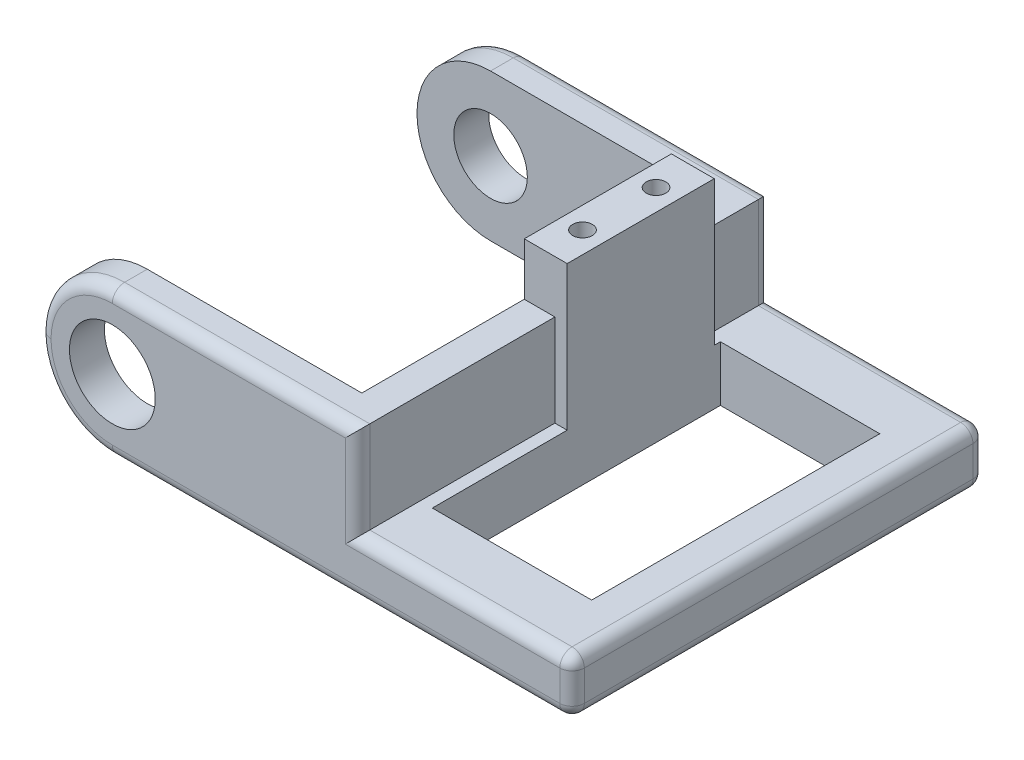
SolidWorks part; units mm, degrees
ref_plane "Front Plane" through (0, 0, 0) normal (0, 0, 1) x (1, 0, 0)
ref_plane "Top Plane" through (0, 0, 0) normal (0, 1, 0) x (1, 0, 0)
ref_plane "Right Plane" through (0, 0, 0) normal (1, 0, 0) x (0, 0, -1)
sketch "Sketch1" plane through (0, 0, 0) normal (1, 0, 0) x (0, 0, -1)
  line L0 (-222.6467, 45.44) -> (-222.6467, 62.0152) construction
  line L1 (-256.3467, 26.069) -> (-222.6467, 26.069)
  line L2 (-256.3467, 26.069) -> (-256.3467, 14.069)
  line L3 (-256.3467, 14.069) -> (-222.6467, 14.069)
  line L4 (-222.6467, 26.069) -> (-222.6467, 14.069)
  dimension "D1" = 12
  dimension "D2" = 33.7
  dimension "D3" = 0
extrude "Boss-Extrude1" add sketch "Sketch1" along normal blind 2.5
sketch "Sketch2" plane through (2.5, 0, 0) normal (1, 0, 0) x (0, 0, -1)
  line L0 (-222.6467, 14.069) -> (-222.6467, 26.069) construction
  line L1 (-256.3467, 14.069) -> (-222.6467, 14.069)
  line L2 (-256.3467, 14.069) -> (-256.3467, 18.569)
  line L3 (-256.3467, 18.569) -> (-222.6467, 18.569)
  line L4 (-222.6467, 14.069) -> (-222.6467, 18.569)
  dimension "D1" = 4.5
extrude "Boss-Extrude2" add sketch "Sketch2" along normal blind 17.5
sketch "Sketch3" plane through (0, 18.569, 0) normal (0, 1, 0) x (1, 0, 0)
  line L0 (2.5, -222.6467) -> (2.5, -256.3467) construction
  line L1 (3.5, -227.7467) -> (16.5, -227.7467)
  line L2 (3.5, -227.7467) -> (3.5, -251.2467)
  line L3 (3.5, -251.2467) -> (16.5, -251.2467)
  line L4 (16.5, -227.7467) -> (16.5, -251.2467)
  line L8 (20, -222.6467) -> (2.5, -222.6467) construction
  dimension "D1" = 1
  dimension "D2" = 23.5
  dimension "D3" = 5.1
  dimension "D4" = 13
extrude "Cut-Extrude1" cut sketch "Sketch3" against normal through all
sketch "Sketch4" plane through (0, 0, 0) normal (-1, 0, 0) x (0, 0, 1)
  line L0 (256.3467, 14.069) -> (222.6467, 14.069) construction
  line L1 (222.6467, 26.069) -> (225.4967, 26.069)
  line L2 (222.6467, 26.069) -> (222.6467, 14.069)
  line L3 (222.6467, 14.069) -> (225.4967, 14.069)
  line L4 (225.4967, 26.069) -> (225.4967, 14.069)
  line L6 (256.3467, 26.069) -> (253.4967, 26.069)
  line L7 (256.3467, 26.069) -> (256.3467, 14.069)
  line L8 (256.3467, 14.069) -> (253.4967, 14.069)
  line L9 (253.4967, 26.069) -> (253.4967, 14.069)
  dimension "D1" = 2.85
  dimension "D2" = 2.85
extrude "Boss-Extrude3" add sketch "Sketch4" along normal blind 23.5
fillet "Fillet1" radius 6 4 edges at (-23.5, 14.069, 224.0717) (-23.5, 26.069, 224.0717) (-23.5, 14.069, 254.9217) (-23.5, 26.069, 254.9217)
sketch "Sketch5" plane through (0, 0, 256.3467) normal (0, 0, 1) x (1, 0, 0)
  circle A0 centre (-17.5, 20.069) radius 3.5
  dimension "D1" = 7
extrude "Cut-Extrude2" cut sketch "Sketch5" against normal blind 4
sketch "Sketch6" plane through (0, 0, 225.4967) normal (0, 0, 1) x (1, 0, 0)
  circle A0 centre (-17.5, 20.069) radius 3
  dimension "D1" = 6
extrude "Cut-Extrude3" cut sketch "Sketch6" against normal blind 4
sketch "Sketch7" plane through (0, 18.569, 0) normal (0, 1, 0) x (1, 0, 0)
  line L0 (3.5, -227.7467) -> (3.5, -251.2467) construction
  line L1 (3.5, -228.2467) -> (0, -228.2467)
  line L2 (3.5, -228.2467) -> (3.5, -240.2467)
  line L3 (3.5, -240.2467) -> (0, -240.2467)
  line L4 (0, -228.2467) -> (0, -240.2467)
  line L5 (0, -225.4967) -> (0, -253.4967) construction
  line L8 (3.5, -228.2467) -> (0, -228.2467) construction
  line L9 (0, -240.2467) -> (3.5, -240.2467) construction
  dimension "D1" = 0
  dimension "D2" = 0
extrude "Boss-Extrude4" add sketch "Sketch7" along normal blind 11.77
fillet "Fillet2" radius 1 16 edges at (-7.5, 26.069, 256.3467) (-21.7426, 24.3116, 256.3467) (-21.7426, 15.8263, 256.3467) (-7.5, 26.069, 222.6467) (-21.7426, 24.3116, 222.6467) (-21.7426, 15.8263, 222.6467) (2.5, 22.319, 222.6467) (2.5, 22.319, 256.3467) (1.25, 14.069, 256.3467) (1.25, 14.069, 222.6467) (20, 16.319, 222.6467) (11.25, 18.569, 222.6467) (20, 14.069, 239.4967) (20, 18.569, 239.4967) (20, 16.319, 256.3467) (11.25, 18.569, 256.3467)
sketch "Sketch8" plane through (0, 30.339, 0) normal (0, 1, 0) x (1, 0, 0)
  circle A0 centre (1.75, -231.2467) radius 0.8
  circle A1 centre (1.75, -237.2467) radius 0.8
extrude "Cut-Extrude4" cut sketch "Sketch8" against normal blind 2
